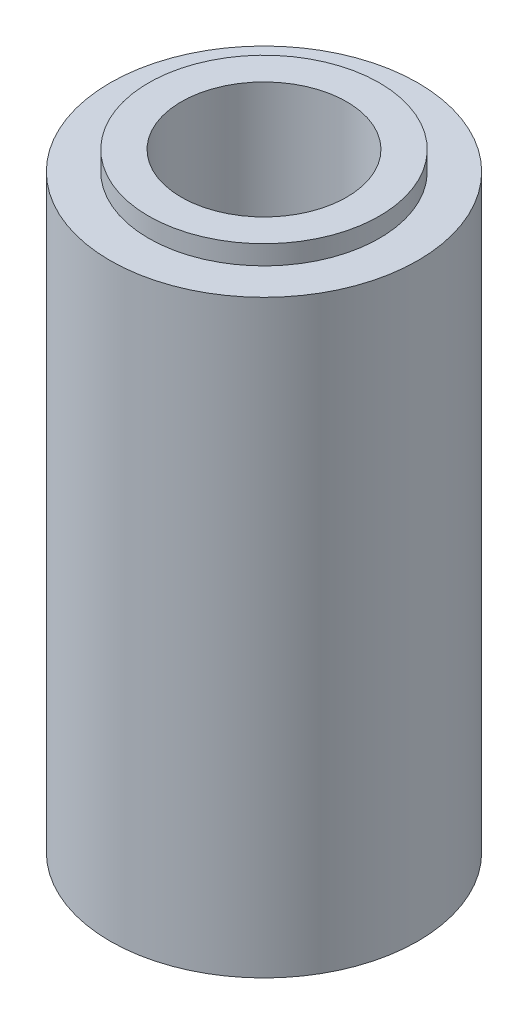
SolidWorks part; units mm, degrees
ref_plane "Front Plane" through (0, 0, 0) normal (0, 0, 1) x (1, 0, 0)
ref_plane "Top Plane" through (0, 0, 0) normal (0, 1, 0) x (1, 0, 0)
ref_plane "Right Plane" through (0, 0, 0) normal (1, 0, 0) x (0, 0, -1)
sketch "Sketch1" plane through (0, 0, 0) normal (0, 1, 0) x (1, 0, 0)
  circle A0 centre (0, 0) radius 4
  dimension "D1" = 8
extrude "Boss-Extrude1" add sketch "Sketch1" along normal blind 15.8188
sketch "Sketch2" plane through (0, 15.8188, 0) normal (0, 1, 0) x (1, 0, 0)
  circle A0 centre (0, 0) radius 3
  dimension "D1" = 6
extrude "Cut-Extrude1" cut sketch "Sketch2" against normal blind 0.5 flip side to cut
hole_wizard "M4 Clearance Hole1" positions "Sketch3" profile "Sketch4" hole size "M4" standard "ANSI Metric" end condition through all
sketch "Sketch3" plane through (0, 15.8188, 0) normal (0, 1, 0) x (1, 0, 0)
  point P0 (0, 0)
sketch "Sketch4" plane through (0, 15.8188, 0) normal (1, 0, 0) x (0, 0, 1)
  line L0 (0, 0) -> (0, 15.8188)
  line L1 (0, 15.8188) -> (2.15, 15.8188)
  line L2 (2.15, 15.8188) -> (2.15, 0)
  line L5 (2.15, 0) -> (0, 0)
  line L11 (0, -6.35) -> (0, 107.95) construction
  dimension "Thru Hole Dia." = 4.3
  dimension "Thru Hole Depth" = 15.8188
